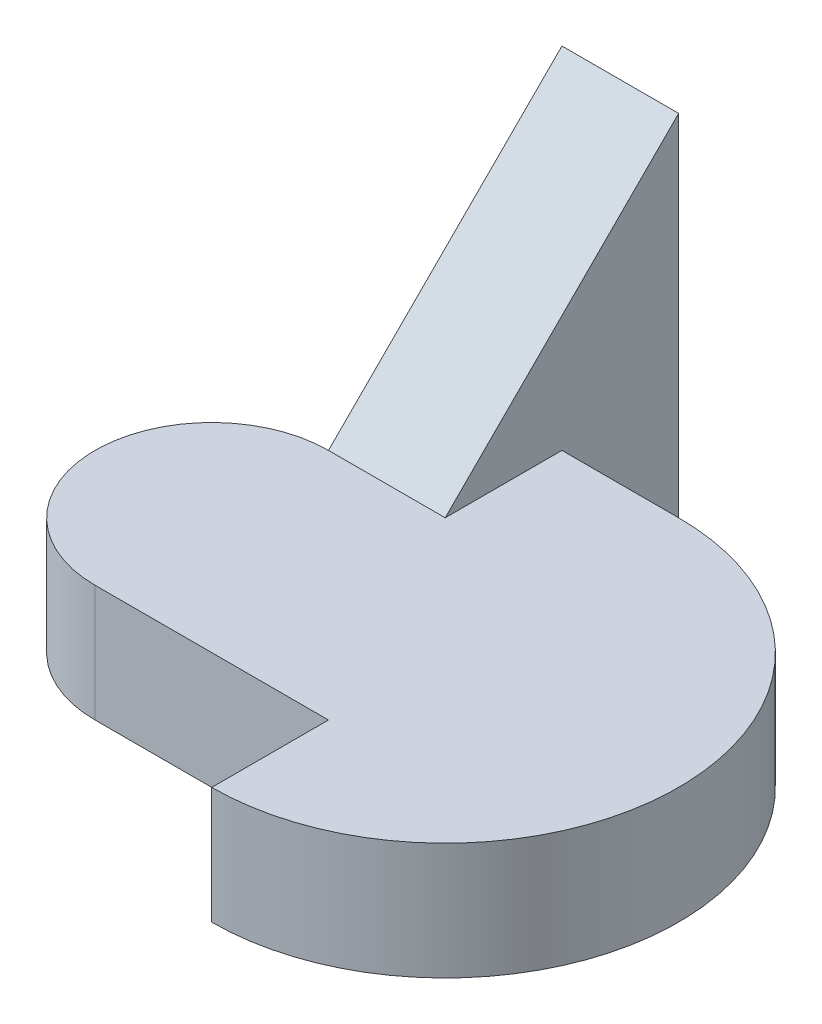
SolidWorks part; units mm, degrees
ref_plane "前基準面" through (0, 0, 0) normal (0, 0, 1) x (1, 0, 0)
ref_plane "上基準面" through (0, 0, 0) normal (0, 1, 0) x (1, 0, 0)
ref_plane "右基準面" through (0, 0, 0) normal (1, 0, 0) x (0, 0, -1)
sketch "草圖1" plane through (0, 0, 0) normal (0, 1, 0) x (1, 0, 0)
  line L0 (0, 0) -> (-10, 0) construction
  line L1 (-10, -5) -> (0, -5)
  line L2 (0, -5) -> (0, -10)
  line L3 (0, 10) -> (-5, 10)
  line L4 (-5, 10) -> (-5, 5)
  line L5 (-5, 5) -> (-10, 5)
  line L7 (-10, 5) -> (-5, 5)
  line L8 (-10, 5) -> (-10, 15)
  line L9 (-10, 15) -> (-5, 15)
  line L10 (-5, 5) -> (-5, 15)
  arc A1 (-10, 5) -> (-10, -5) centre (-10, 0) ccw
  arc A2 (0, -10) -> (0, 10) centre (0, 0) ccw
  dimension "D1" = 10
  dimension "D3" = 10
  dimension "D4" = 5
  dimension "D5" = 10
extrude "填料-伸長1" add sketch "草圖1" along normal blind 5 contours L2 A2 L3 L4 L5 A1 L1 region at (-1.1572, 0, -0.5835)
extrude "填料-伸長2" add sketch "草圖1<3>" along normal blind 15 contours L4 L10 L9 L8 L5 region at (-7.5, 0, -10)
sketch "草圖1<3>" plane through (0, 0, 0) normal (0, 1, 0) x (1, 0, 0) same geometry as "草圖1"
sketch "草圖2" plane through (-10, 0, 0) normal (-1, 0, 0) x (0, 0, 1)
  line L0 (-15, 15) -> (-5, 5)
  line L1 (-5, 5) -> (-5, 15)
  line L2 (-5, 15) -> (-15, 15)
extrude "除料-伸長1" cut sketch "草圖2" against normal blind 15
scale "縮放比例1" scale about centroid uniform scaling yes scale factor 0.2
